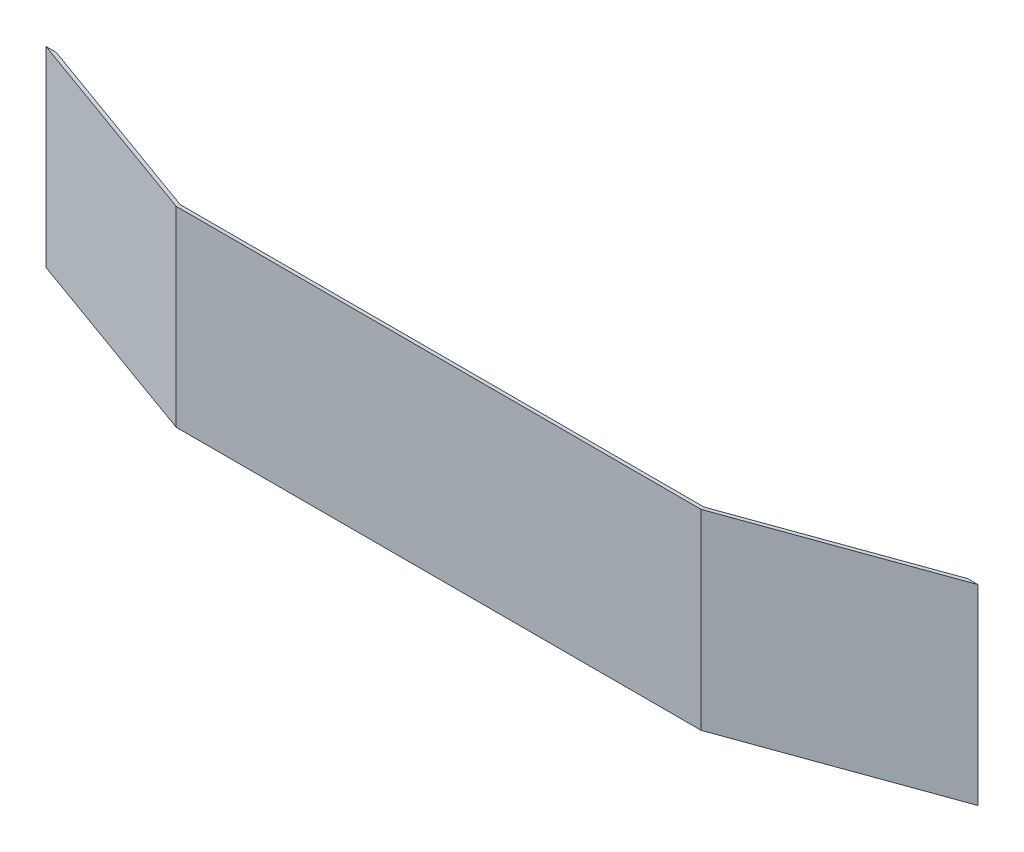
SolidWorks part; units mm, degrees
ref_plane "Front Plane" through (0, 0, 0) normal (0, 0, 1) x (1, 0, 0)
ref_plane "Top Plane" through (0, 0, 0) normal (0, 1, 0) x (1, 0, 0)
ref_plane "Right Plane" through (0, 0, 0) normal (1, 0, 0) x (0, 0, -1)
sketch "Sketch1" plane through (0, 0, 0) normal (0, 1, 0) x (1, 0, 0)
  line L0 (-261, -120) -> (-150, -160)
  line L1 (-150, -160) -> (150, -160)
  line L2 (150, -160) -> (261, -120)
  line L3 (261, -120) -> (-261, -120) construction
  line L5 (-150.3494, -162) -> (150.3494, -162)
  line L8 (-257.4765, -120) -> (-261, -120)
  line L9 (-261, -120) -> (-266.8994, -120)
  line L10 (261, -120) -> (266.8994, -120)
  line L11 (-272.4494, -118) -> (-150.3494, -162) construction
  line L12 (266.8994, -120) -> (150.3494, -162)
  line L13 (150.3494, -162) -> (272.4494, -118) construction
  line L14 (272.4494, -118) -> (-272.4494, -118) construction
  line L15 (-150.3494, -162) -> (-266.8994, -120)
  dimension "D1" = 2
extrude "Boss-Extrude1" add sketch "Sketch1" along normal blind 109.6 contours L0 L1 L2 L10 L12 L5 L15 L9
equation "\"gap\"= 1mm"
equation "\"casewidth\"= 2mm"
